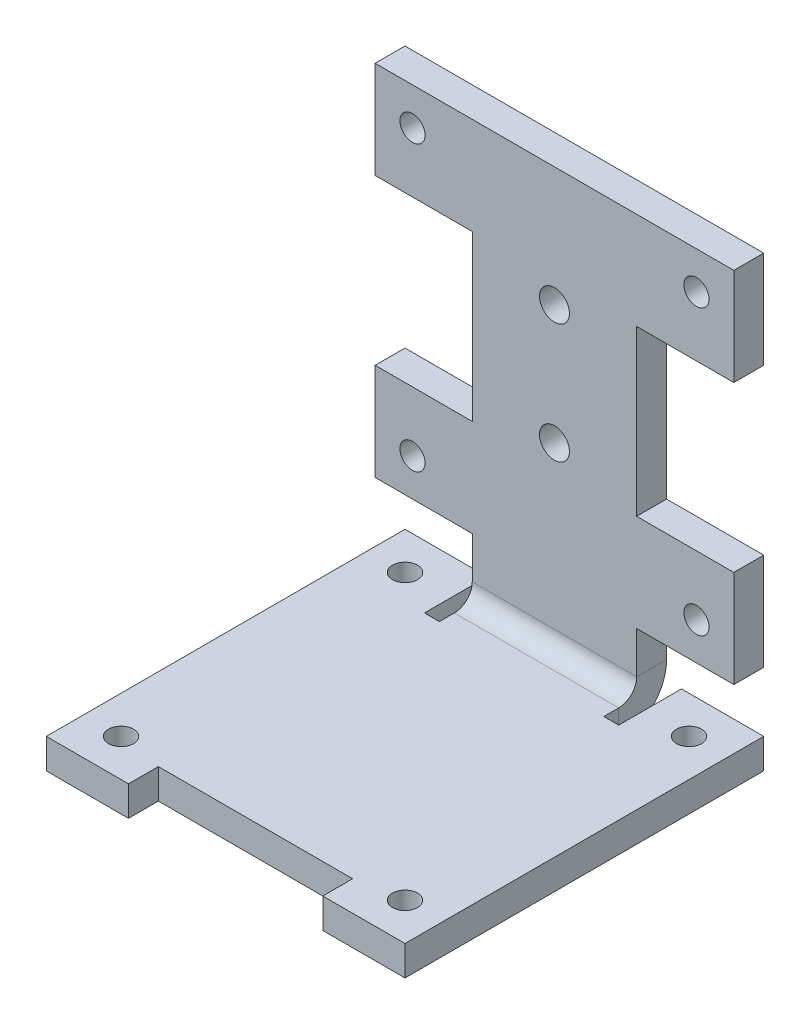
SolidWorks part; units mm, degrees
note: The reader was unsure of these and kept them because the rebuilt part matched: flange length of "边线-法兰1".
ref_plane "前视基准面" through (0, 0, 0) normal (0, 0, 1) x (1, 0, 0)
ref_plane "上视基准面" through (0, 0, 0) normal (0, 1, 0) x (1, 0, 0)
ref_plane "右视基准面" through (0, 0, 0) normal (1, 0, 0) x (0, 0, -1)
other "Configuration Table"
sketch "草图1" plane through (0, 0, 0) normal (0, 1, 0) x (1, 0, 0)
  line L0 (-16.25, 25) -> (-16.25, 30)
  line L1 (-30, -30) -> (-16.25, -30)
  line L2 (-30, -30) -> (-30, 30)
  line L3 (-30, 30) -> (-16.25, 30)
  line L4 (30, -30) -> (30, 30)
  line L5 (-30, -30) -> (30, 30) construction
  line L6 (-30, 30) -> (30, -30) construction
  line L7 (-23.75, -23.75) -> (23.75, -23.75) construction
  line L8 (-23.75, -23.75) -> (-23.75, 23.75) construction
  line L9 (-23.75, 23.75) -> (23.75, 23.75) construction
  line L10 (23.75, -23.75) -> (23.75, 23.75) construction
  line L11 (-23.75, -23.75) -> (23.75, 23.75) construction
  line L12 (-23.75, 23.75) -> (23.75, -23.75) construction
  line L14 (-16.25, -30) -> (-16.25, -25)
  line L16 (16.25, -30) -> (16.25, -25)
  line L17 (-16.25, -30) -> (16.25, 30) construction
  line L18 (-16.25, 30) -> (16.25, -30) construction
  line L19 (-16.25, -25) -> (16.25, -25)
  line L21 (-16.25, 25) -> (16.25, 25)
  line L23 (-16.25, -25) -> (16.25, 25) construction
  line L24 (-16.25, 25) -> (16.25, -25) construction
  line L26 (16.25, 25) -> (16.25, 30)
  line L27 (16.25, -30) -> (30, -30)
  line L28 (16.25, 30) -> (30, 30)
  circle A0 centre (-23.75, 23.75) radius 2.1
  circle A1 centre (23.75, 23.75) radius 2.1
  circle A2 centre (-23.75, -23.75) radius 2.1
  circle A3 centre (23.75, -23.75) radius 2.1
  point P0 (0, 0)
  point P6 (0, 0)
  point P15 (0, 0)
  point P20 (0, 0)
  dimension "D4" = 4.2
  dimension "D5" = 4.2
  dimension "D6" = 4.2
  dimension "D7" = 4.2
  dimension "D1" = 60
  dimension "D2" = 60
  dimension "D3" = 47.5
  dimension "D8" = 32.5
  dimension "D9" = 50
base flange "基体-法兰1" sketch "草图1" thickness 5 reverse thickness direction no parameters "D1"=0.7366
edge flange "边线-法兰1" sketch "草图8" flange angle 90 flange length 75 flange position material outside bend radius 3 thickness 5 parameters "D6"=10
sketch "草图8" plane through (0, 0, -25) normal (0, 0, -1) x (-1, 0, 0)
  line L5 (-16.25, 0) -> (16.25, 0) construction
  line L6 (-13.75, 70) -> (13.75, 70)
  line L7 (-13.75, 70) -> (-13.75, 0)
  line L8 (-13.75, 0) -> (13.75, 0)
  line L9 (13.75, 70) -> (13.75, 0)
  point P6 (0, 70)
  dimension "D1" = 27.5
  dimension "D2" = 70
bend "边线折弯1" bend radius 3 bend angle 90 parameters "D5"=1
sketch "草图9" plane through (0, 0, 0) normal (0, 0, 1) x (1, 0, 0)
  line L0 (-13.75, 70) -> (13.75, 70) construction
  line L1 (30, 70) -> (-30, 70) construction
  line L2 (30, 70) -> (30, 10) construction
  line L3 (30, 10) -> (-30, 10) construction
  line L4 (-30, 70) -> (-30, 10) construction
  line L5 (-13.75, 3) -> (-13.75, 70) construction
  line L6 (-30, 70) -> (-13.75, 70)
  line L7 (-30, 70) -> (-30, 53.75)
  line L8 (-30, 53.75) -> (-13.75, 53.75)
  line L9 (-13.75, 70) -> (-13.75, 53.75)
  line L10 (13.75, 70) -> (13.75, 3) construction
  line L11 (30, 70) -> (13.75, 70)
  line L12 (30, 70) -> (30, 53.75)
  line L13 (30, 53.75) -> (13.75, 53.75)
  line L14 (13.75, 70) -> (13.75, 53.75)
  line L16 (-30, 10) -> (-13.75, 10)
  line L17 (-30, 10) -> (-30, 26.25)
  line L18 (-30, 26.25) -> (-13.75, 26.25)
  line L19 (-13.75, 10) -> (-13.75, 26.25)
  line L20 (30, 10) -> (13.75, 10)
  line L21 (30, 10) -> (30, 26.25)
  line L22 (30, 26.25) -> (13.75, 26.25)
  line L23 (13.75, 10) -> (13.75, 26.25)
  point P6 (0, 70)
  dimension "D1" = 60
  dimension "D2" = 60
  dimension "D3" = 16.25
  dimension "D4" = 16.25
extrude "凸台-拉伸1" add sketch "草图9" along normal up to surface (5 mm away) from surface at -30 up to face at (0, 36.5, -25) starting at face at (0, 36.5, -30)
sketch "草图10" plane through (0, 0, 0) normal (0, 0, 1) x (1, 0, 0)
  line L5 (-30, 70) -> (30, 10) construction
  line L6 (30, 70) -> (-30, 10) construction
  line L7 (0, 30) -> (0, 50) construction
  circle A0 centre (0, 50) radius 2.5
  circle A1 centre (0, 30) radius 2.5
  point P13 (0, 40)
  dimension "D2" = 5
  dimension "D3" = 5
  dimension "D1" = 20
extrude "切除-拉伸1" cut sketch "草图10" against normal up to surface (5 mm away) from surface
sketch "草图11" plane through (0, 0, 0) normal (0, 0, 1) x (1, 0, 0)
  line L0 (30, 10) -> (-30, 70) construction
  line L1 (-30, 10) -> (30, 70) construction
  line L3 (-23.75, 16.25) -> (23.75, 16.25) construction
  line L4 (-23.75, 16.25) -> (-23.75, 63.75) construction
  line L5 (-23.75, 63.75) -> (23.75, 63.75) construction
  line L6 (23.75, 16.25) -> (23.75, 63.75) construction
  line L7 (-23.75, 16.25) -> (23.75, 63.75) construction
  line L8 (-23.75, 63.75) -> (23.75, 16.25) construction
  circle A0 centre (-23.75, 16.25) radius 2.1
  circle A1 centre (-23.75, 63.75) radius 2.1
  circle A2 centre (23.75, 63.75) radius 2.1
  circle A3 centre (23.75, 16.25) radius 2.1
  point P8 (0, 40)
  dimension "D2" = 4.2
  dimension "D3" = 4.2
  dimension "D4" = 4.2
  dimension "D5" = 4.2
  dimension "D1" = 47.5
extrude "切除-拉伸2" cut sketch "草图11" against normal up to surface (5 mm away) from surface
sketch "折弯-线1" plane through (0, 0, 0) normal (0, 1, 0) x (1, 0, 0)
sketch "边界框1" plane through (0, 0, 0) normal (0, 1, 0) x (1, 0, 0)
sheet metal parameters "钣金6" thickness 5 parameters "D1"=0.7366
flat pattern "平板型式6" [suppressed]
sketch "折弯-线2" plane through (0, 0, 0) normal (0, 1, 0) x (1, 0, 0)
sketch "边界框2" [suppressed] plane through (0, 0, 0) normal (0, 1, 0) x (1, 0, 0)
sheet metal parameters "钣金7" thickness 5 parameters "D1"=0.7366
flat pattern "平板型式6" [suppressed]
sketch "折弯-线2" plane through (0, 0, 0) normal (0, 1, 0) x (1, 0, 0)
sketch "边界框2" [suppressed] plane through (0, 0, 0) normal (0, 1, 0) x (1, 0, 0)
bend of the flat pattern "展平-<边线折弯1>1"
sheet metal parameters "钣金8" thickness 5 parameters "D1"=0.7366
flat pattern "平板型式6" [suppressed]
sketch "折弯-线2" plane through (0, 0, 0) normal (0, 1, 0) x (1, 0, 0)
sketch "边界框2" [suppressed] plane through (0, 0, 0) normal (0, 1, 0) x (1, 0, 0)
bend of the flat pattern "展平-<边线折弯1>1"
sheet metal parameters "钣金9" thickness 5 parameters "D1"=0.7366
flat pattern "平板型式6" [suppressed]
sketch "折弯-线2" plane through (0, 0, 0) normal (0, 1, 0) x (1, 0, 0)
sketch "边界框2" [suppressed] plane through (0, 0, 0) normal (0, 1, 0) x (1, 0, 0)
bend of the flat pattern "展平-<边线折弯1>1"
sheet metal parameters "钣金10" thickness 5 parameters "D1"=0.7366
flat pattern "平板型式6" [suppressed]
sketch "折弯-线2" plane through (0, 0, 0) normal (0, 1, 0) x (1, 0, 0)
sketch "边界框2" [suppressed] plane through (0, 0, 0) normal (0, 1, 0) x (1, 0, 0)
bend of the flat pattern "展平-<边线折弯1>1"
